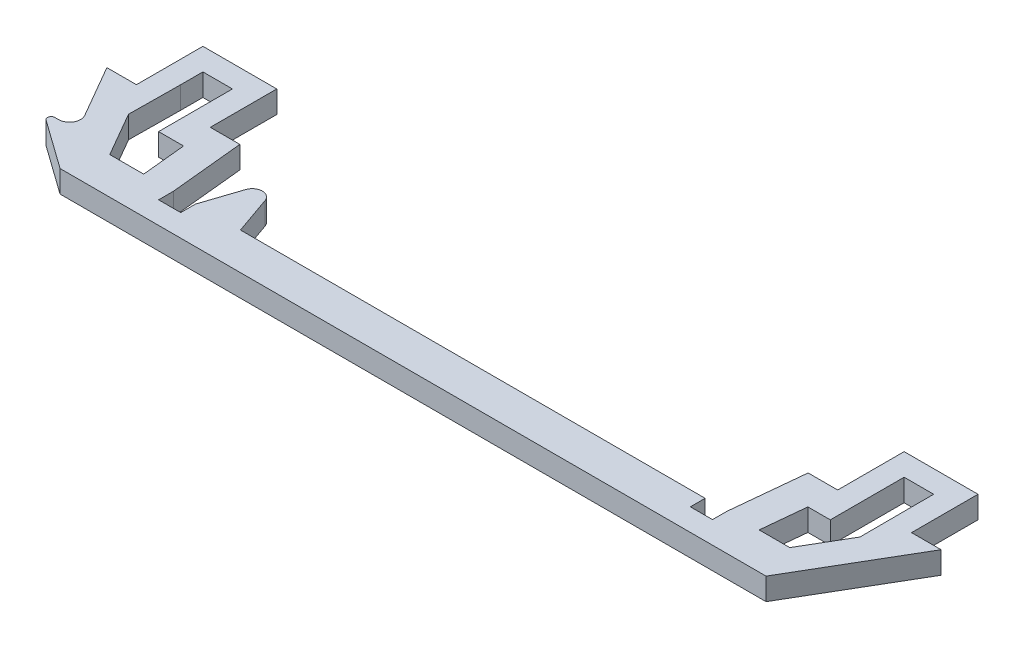
SolidWorks part; units mm, degrees
material "Custom Plastic"
ref_plane "Front Plane" through (0, 0, 0) normal (0, 0, 1) x (1, 0, 0)
ref_plane "Top Plane" through (0, 0, 0) normal (0, 1, 0) x (1, 0, 0)
ref_plane "Right Plane" through (0, 0, 0) normal (1, 0, 0) x (0, 0, -1)
sketch "Sketch1" plane through (0, 0, 0) normal (0, 1, 0) x (1, 0, 0)
  line L0 (-62.4186, -47.1587) -> (-58.4186, -47.1587)
  line L1 (-58.4186, -47.1587) -> (-58.4186, -38.1587)
  line L2 (-58.4186, -38.1587) -> (-48.4186, -38.1587)
  line L3 (-48.4186, -38.1587) -> (-48.4186, -47.1587)
  line L4 (-48.4186, -47.1587) -> (-44.4186, -47.1587)
  line L5 (-44.4186, -47.1587) -> (-43.4188, -57.1562)
  line L7 (31.5814, -57.2088) -> (32.5814, -47.2113)
  line L8 (32.5814, -47.2113) -> (36.5814, -47.2113)
  line L9 (36.5814, -47.2113) -> (36.5814, -38.2113)
  line L10 (36.5814, -38.2113) -> (46.5814, -38.2113)
  line L11 (46.5814, -38.2113) -> (46.5814, -47.2113)
  line L12 (46.5814, -47.2113) -> (50.5814, -47.2113)
  line L13 (50.5814, -47.2113) -> (41.8306, -62.1587)
  line L14 (41.8306, -62.1587) -> (-53.7583, -62.1587)
  line L15 (-58.3105, -54.274) -> (-62.4186, -47.1587)
  line L16 (36.5478, -51.2113) -> (39.5814, -51.2113)
  line L17 (-55.4186, -41.1587) -> (-51.4186, -41.1587)
  line L18 (-55.4186, -41.1587) -> (-55.4186, -44.1587)
  line L20 (-51.4186, -41.1587) -> (-51.4186, -44.1587)
  line L21 (39.5814, -41.2113) -> (43.5814, -41.2113)
  line L22 (39.5814, -41.2113) -> (39.5814, -44.2113)
  line L24 (43.5814, -41.2113) -> (43.5814, -44.2113)
  line L25 (43.6046, -51.2113) -> (40.0934, -57.2088)
  line L26 (40.0934, -57.2088) -> (35.9479, -57.2088)
  line L27 (35.9479, -57.2088) -> (36.5478, -51.2113)
  line L28 (-51.4186, -51.1587) -> (-48.0385, -51.1587)
  line L29 (-48.0385, -51.1587) -> (-47.4385, -57.1587)
  line L30 (-47.4385, -57.1587) -> (-52.0263, -57.1587)
  line L31 (-52.0263, -57.1587) -> (-55.4904, -51.1587)
  line L32 (28.5814, -57.1587) -> (28.5814, -59.1587)
  line L33 (28.5814, -47.1587) -> (28.5814, -62.1587) construction
  line L34 (28.5814, -59.1587) -> (31.5814, -59.1587)
  line L35 (31.5814, -59.1587) -> (31.5814, -57.2088)
  line L36 (31.5814, -62.1587) -> (31.5814, -47.1587) construction
  line L38 (-43.4188, -57.1562) -> (-43.4188, -59.1587)
  line L39 (-43.4188, -59.1587) -> (-40.4188, -59.1587)
  line L40 (-40.4188, -59.1587) -> (-40.4188, -57.1587)
  line L41 (-34.3352, -57.1587) -> (28.5814, -57.1587)
  line L42 (-34.3352, -57.1587) -> (-36.1291, -52.0241)
  line L43 (43.5814, -44.2113) -> (43.6046, -51.2113)
  line L44 (-38.7227, -52.0447) -> (-40.4188, -57.1587)
  line L45 (39.5814, -44.2113) -> (39.5814, -51.2113)
  line L46 (-55.4186, -44.1587) -> (-55.4904, -51.1587)
  line L47 (-51.4186, -44.1587) -> (-51.4186, -51.1587)
  line L48 (-53.7583, -62.1587) -> (-60.3821, -57.431)
  line L49 (-60.0916, -56.524) -> (-59.6096, -56.524)
  arc A0 (-38.7227, -52.0447) -> (-36.1291, -52.0241) centre (-37.4224, -52.4759) cw
  arc A1 (-59.6096, -56.524) -> (-58.3105, -54.274) centre (-59.6096, -55.024) ccw
  arc A2 (-60.3821, -57.431) -> (-60.0916, -56.524) centre (-60.0916, -57.024) cw
  dimension "D6" = 0.5
  dimension "D5" = 1.5
  dimension "D1" = 15
  dimension "D2" = 4
  dimension "D3" = 9
  dimension "D4" = 3
  dimension "D7" = 120
  dimension "D8" = 10
  dimension "D9" = 85
  dimension "D10" = 3
  dimension "D12" = 3
  dimension "D13" = 3
  dimension "D14" = 3
  dimension "D15" = 3
  dimension "D17" = 4
  dimension "D18" = 4
  dimension "D19" = 4
  dimension "D20" = 4
  dimension "D21" = 4
  dimension "D23" = 2
  dimension "D24" = 3
extrude "Boss-Extrude1" add sketch "Sketch1" along normal blind 3
